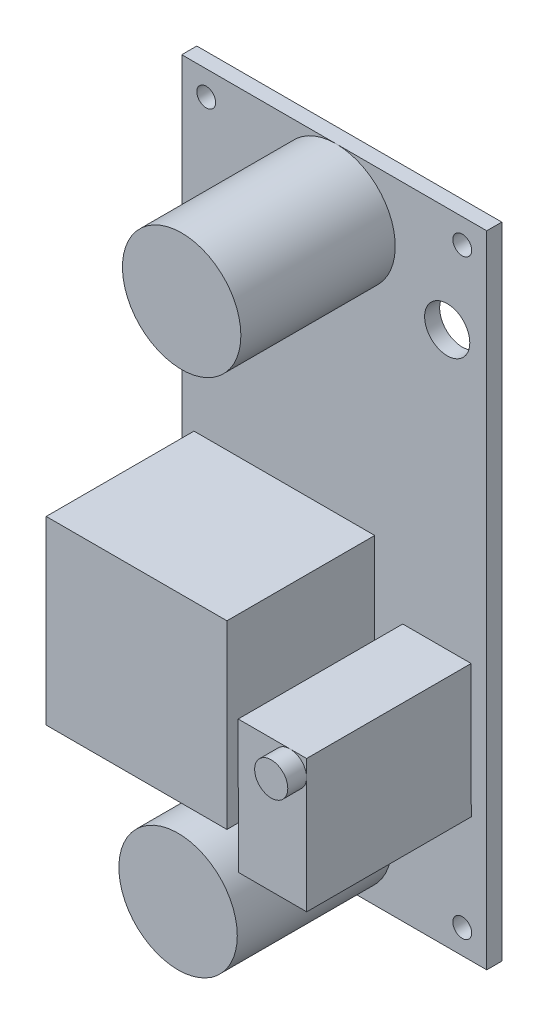
SolidWorks part; units mm, degrees
ref_plane "Front Plane" through (0, 0, 0) normal (0, 0, 1) x (1, 0, 0)
ref_plane "Top Plane" through (0, 0, 0) normal (0, 1, 0) x (1, 0, 0)
ref_plane "Right Plane" through (0, 0, 0) normal (1, 0, 0) x (0, 0, -1)
sketch "Sketch1" plane through (0, 0, 0) normal (0, 0, 1) x (1, 0, 0)
  line L1 (0, 43.18) -> (20.574, 43.18)
  line L2 (0, 43.18) -> (0, 0)
  line L3 (0, 0) -> (20.574, 0)
  line L4 (20.574, 43.18) -> (20.574, 0)
  dimension "D1" = 43.18
  dimension "D2" = 20.574
extrude "Boss-Extrude1" add sketch "Sketch1" along normal blind 1.016
sketch "Sketch2" plane through (0, 0, 1.016) normal (0, 0, 1) x (1, 0, 0)
  line L0 (17.907, 36.068) -> (20.574, 36.068) construction
  line L1 (17.907, 43.18) -> (17.907, 36.068) construction
  line L2 (0, 6.35) -> (3.0988, 6.35) construction
  line L3 (3.0988, 0) -> (3.0988, 6.35) construction
  line L4 (0, 0) -> (20.574, 0) construction
  line L5 (0, 43.18) -> (0, 0) construction
  line L6 (20.574, 0) -> (20.574, 43.18) construction
  line L7 (20.574, 43.18) -> (0, 43.18) construction
  circle A0 centre (17.907, 36.068) radius 1.524
  circle A1 centre (3.0988, 6.35) radius 1.524
  dimension "D5" = 3.048
  dimension "D1" = 7.112
  dimension "D2" = 6.35
  dimension "D3" = 2.667
  dimension "D4" = 3.0988
extrude "Cut-Extrude1" cut sketch "Sketch2" against normal through all
sketch "Sketch3" plane through (0, 0, 1.016) normal (0, 0, 1) x (1, 0, 0)
  line L0 (18.923, 43.18) -> (18.923, 41.529) construction
  line L1 (18.923, 41.529) -> (20.574, 41.529) construction
  line L2 (1.651, 43.18) -> (1.651, 41.529) construction
  line L3 (0, 41.529) -> (1.651, 41.529) construction
  line L4 (1.651, 0) -> (1.651, 1.651) construction
  line L5 (0, 1.651) -> (1.651, 1.651) construction
  line L6 (18.923, 1.651) -> (18.923, 0) construction
  line L7 (20.574, 1.651) -> (18.923, 1.651) construction
  line L8 (20.574, 43.18) -> (0, 43.18) construction
  line L9 (0, 43.18) -> (0, 0) construction
  line L10 (20.574, 0) -> (20.574, 43.18) construction
  line L11 (0, 0) -> (20.574, 0) construction
  circle A0 centre (18.923, 41.529) radius 0.635
  circle A1 centre (18.923, 1.651) radius 0.635
  circle A2 centre (1.651, 1.651) radius 0.635
  circle A3 centre (1.651, 41.529) radius 0.635
  dimension "D1" = 1.27
  dimension "D2" = 1.651
extrude "Cut-Extrude2" cut sketch "Sketch3" against normal blind 2.54
sketch "Sketch4" plane through (0, 0, 0) normal (0, 0, -1) x (-1, 0, 0)
  line L0 (-17.4213, 43.18) -> (-17.4213, 40.386) construction
  line L1 (-17.4213, 0) -> (-17.4213, 3.9936) construction
  line L2 (0, 40.386) -> (-20.574, 40.386) construction
  line L3 (0, 43.18) -> (0, 0) construction
  line L4 (-20.574, 43.18) -> (0, 43.18) construction
  line L6 (-2.4416, 43.18) -> (-2.4416, 40.386) construction
  line L7 (-2.4416, 0) -> (-2.4416, 3.9936) construction
  line L8 (-20.574, 0) -> (-20.574, 43.18) construction
  line L9 (0, 0) -> (-20.574, 0) construction
  line L10 (0, 3.9936) -> (-20.574, 3.9936) construction
  line L11 (0, 43.18) -> (0, 0) construction
  text T0 "IN+" font "Century Gothic" height in points 3
  text T1 "IN-" font "Century Gothic" height in points 3
  text T2 "OUT+" font "Century Gothic" height in points 3
  text T3 "OUT-" font "Century Gothic" height in points 3
  dimension "D1" = 3.9936
  dimension "D2" = 2.794
extrude "Boss-Extrude2" add sketch "Sketch4" along normal blind 0.0025
sketch "Sketch5" plane through (0, 0, 1.016) normal (0, 0, 1) x (1, 0, 0)
  line L0 (0, 15.5067) -> (0.8255, 15.5067) construction
  line L1 (0.8255, 21.6027) -> (13.0175, 21.6027)
  line L2 (0.8255, 21.6027) -> (0.8255, 9.4107)
  line L3 (0.8255, 9.4107) -> (13.0175, 9.4107)
  line L4 (13.0175, 21.6027) -> (13.0175, 9.4107)
  line L5 (6.9215, 9.4107) -> (6.9215, 0) construction
  line L6 (0, 0) -> (20.574, 0) construction
  line L7 (20.574, 0) -> (20.574, 43.18) construction
  line L9 (0, 43.18) -> (0, 0) construction
  dimension "D1" = 12.192
  dimension "D2" = 0.8255
  dimension "D3" = 9.4107
extrude "Boss-Extrude3" add sketch "Sketch5" along normal blind 9.9695
sketch "Sketch6" plane through (0, 0, 1.016) normal (0, 0, 1) x (1, 0, 0)
  line L0 (10.1664, 3.9942) -> (20.574, 3.9942) construction
  line L1 (10.4076, 43.18) -> (10.4076, 39.1858) construction
  line L2 (0, 39.1858) -> (10.4076, 39.1858) construction
  line L3 (20.574, 43.18) -> (0, 43.18) construction
  line L4 (0, 43.18) -> (0, 0) construction
  line L5 (10.1664, 3.9942) -> (10.1664, 0) construction
  line L7 (0, 0) -> (20.574, 0) construction
  line L8 (20.574, 0) -> (20.574, 43.18) construction
  circle A0 centre (10.4076, 39.1858) radius 3.9942
  circle A1 centre (10.1664, 3.9942) radius 3.9941
  dimension "D1" = 7.9883
  dimension "D2" = 3.9942
  dimension "D3" = 10.4076
extrude "Boss-Extrude4" add sketch "Sketch6" along normal blind 10.414
sketch "Sketch7" plane through (0, 0, 1.016) normal (0, 0, 1) x (1, 0, 0)
  line L1 (14.9073, 17.3744) -> (19.5214, 17.3744)
  line L2 (14.9073, 17.3744) -> (14.9159, 8.4201)
  line L3 (14.9159, 8.4201) -> (19.53, 8.4201)
  line L4 (19.5214, 17.3744) -> (19.53, 8.4201)
  line L5 (10.4076, 43.18) -> (0, 43.18) construction
  point P4 (0, 0)
extrude "Boss-Extrude5" add sketch "Sketch7" along normal blind 11.0998
sketch "Sketch8" plane through (0, 0, 12.1158) normal (0, 0, 1) x (1, 0, 0)
  line L0 (19.5225, 16.2568) -> (18.4049, 16.2568) construction
  line L1 (18.4049, 17.3744) -> (18.4049, 16.2568) construction
  line L2 (19.5214, 17.3744) -> (14.9073, 17.3744) construction
  line L3 (19.53, 8.4201) -> (19.5214, 17.3744) construction
  circle A0 centre (18.4049, 16.2568) radius 1.1176
  dimension "D1" = 2.2352
  dimension "D2" = 1.1176
  dimension "D3" = 1.1176
extrude "Boss-Extrude6" add sketch "Sketch8" along normal blind 1.27
